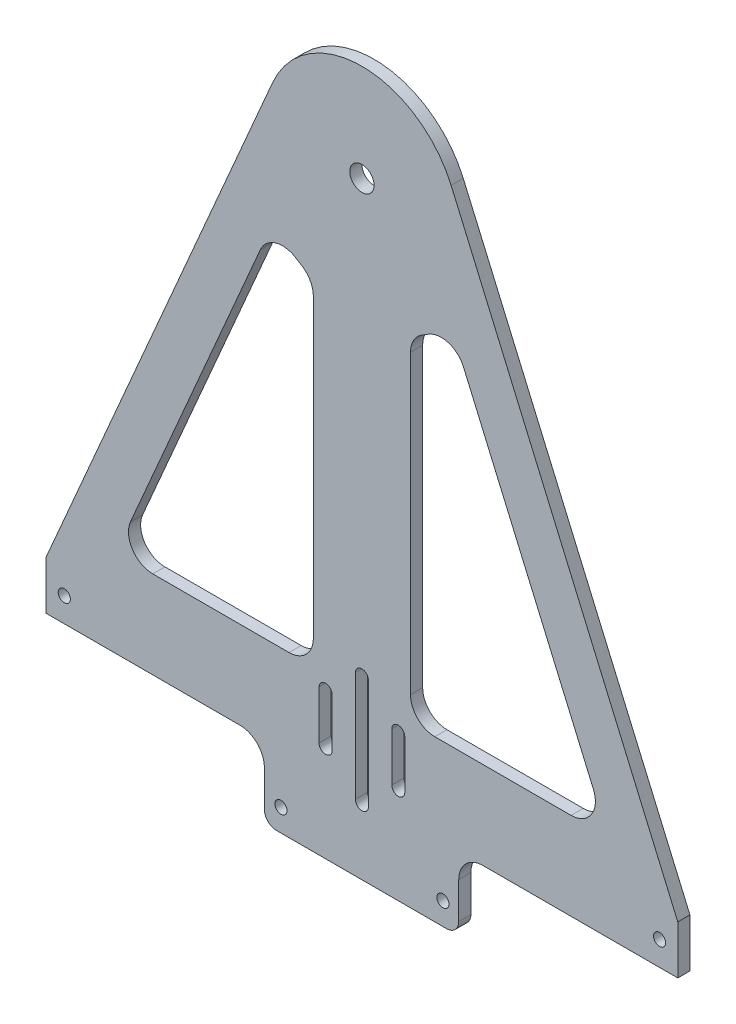
SolidWorks part; units mm, degrees
material "Hexcel AS4C (3000 Filaments)"
ref_plane "Front Plane" through (0, 0, 0) normal (0, 0, 1) x (1, 0, 0)
ref_plane "Top Plane" through (0, 0, 0) normal (0, 1, 0) x (1, 0, 0)
ref_plane "Right Plane" through (0, 0, 0) normal (1, 0, 0) x (0, 0, -1)
sketch "Sketch1" plane through (0, 0, 0) normal (0, 0, 1) x (1, 0, 0)
  line L0 (0, -58.42) -> (0, 58.42) construction
  line L2 (-82.55, 55.7897) -> (-82.55, -52.07)
  line L3 (-76.2, -58.42) -> (76.2, -58.42)
  line L4 (82.55, 55.7897) -> (82.55, -52.07)
  line L5 (-82.55, 58.42) -> (82.55, -58.42) construction
  line L6 (-82.55, -58.42) -> (82.55, 58.42) construction
  line L7 (-80.6901, 60.2799) -> (-75.4296, 65.5404)
  line L8 (-70.9395, 67.4003) -> (-50.8, 67.4003)
  line L9 (-46.3099, 65.5404) -> (-41.0494, 60.2799)
  line L10 (46.3099, 65.5404) -> (41.0494, 60.2799)
  line L11 (70.9395, 67.4003) -> (50.8, 67.4003)
  line L12 (80.6901, 60.2799) -> (75.4296, 65.5404)
  line L13 (-73.5697, 67.4003) -> (-82.55, 67.4003) construction
  line L14 (-82.55, 67.4003) -> (-82.55, 58.42) construction
  line L15 (-36.5592, 58.42) -> (0, 58.42)
  line L16 (0, 58.42) -> (36.5592, 58.42)
  circle A0 centre (-77.7875, -35.052) radius 1.5875
  circle A1 centre (-77.7875, -11.684) radius 1.5875
  circle A2 centre (-77.7875, 11.684) radius 1.5875
  circle A3 centre (-77.7875, 35.052) radius 1.5875
  circle A4 centre (77.7875, 35.052) radius 1.5875
  circle A5 centre (77.7875, 11.684) radius 1.5875
  circle A6 centre (77.7875, -11.684) radius 1.5875
  circle A7 centre (77.7875, -35.052) radius 1.5875
  arc A8 (82.55, 55.7897) -> (80.6901, 60.2799) centre (76.2, 55.7897) ccw
  arc A9 (75.4296, 65.5404) -> (70.9395, 67.4003) centre (70.9395, 61.0503) ccw
  arc A10 (46.3099, 65.5404) -> (50.8, 67.4003) centre (50.8, 61.0503) cw
  arc A11 (41.0494, 60.2799) -> (36.5592, 58.42) centre (36.5592, 64.77) cw
  arc A12 (-36.5592, 58.42) -> (-41.0494, 60.2799) centre (-36.5592, 64.77) cw
  arc A13 (-46.3099, 65.5404) -> (-50.8, 67.4003) centre (-50.8, 61.0503) ccw
  arc A14 (-70.9395, 67.4003) -> (-75.4296, 65.5404) centre (-70.9395, 61.0503) ccw
  arc A15 (-82.55, 55.7897) -> (-80.6901, 60.2799) centre (-76.2, 55.7897) cw
  arc A16 (76.2, -58.42) -> (82.55, -52.07) centre (76.2, -52.07) ccw
  arc A17 (-76.2, -58.42) -> (-82.55, -52.07) centre (-76.2, -52.07) cw
  circle A18 centre (-70.9395, 61.0503) radius 1.5875
  circle A19 centre (-50.8, 61.0503) radius 1.5875
  circle A20 centre (50.8, 61.0503) radius 1.5875
  circle A21 centre (70.9395, 61.0503) radius 1.5875
  point P0 (0, 0)
  point P36 (73.5697, 67.4003)
  point P39 (48.1697, 67.4003)
  point P42 (39.1895, 58.42)
  point P45 (-39.1895, 58.42)
  point P48 (-48.1697, 67.4003)
  dimension "D3" = 3.175
  dimension "D11" = 6.35
  dimension "D12" = 6.35
  dimension "D13" = 3.175
  dimension "D14" = 3.175
  dimension "D1" = 165.1
  dimension "D2" = 116.84
  dimension "D4" = 23.368
  dimension "D5" = 4.7625
  dimension "D7" = 46.736
  dimension "D8" = 12.7
  dimension "D9" = 135
  dimension "D10" = 25.4
  dimension "D6" = 4
extrude "Boss-Extrude1" [suppressed] add sketch "Sketch1" along normal blind 1.5
sketch "Sketch2" [suppressed] plane through (0, 0, 1.5) normal (0, 0, 1) x (1, 0, 0)
  line L0 (0, -45.72) -> (0, 6.3634) construction
  line L1 (0, -58.42) -> (0, 63.5) construction
  line L3 (-82.55, 1.8599) -> (82.55, 1.8599) construction
  line L4 (-82.55, 55.7897) -> (-82.55, -52.07) construction
  line L5 (82.55, -52.07) -> (82.55, 55.7897) construction
  line L7 (-76.2, -58.42) -> (76.2, -58.42) construction
  circle A0 centre (0, -45.72) radius 1.9062
  circle A1 centre (0, 6.3634) radius 1.9062
  dimension "D2" = 3.8125
  dimension "D3" = 3.8125
  dimension "D1" = 52.0834
  dimension "D4" = 12.7
extrude "Cut-Extrude1" [suppressed] cut sketch "Sketch2" against normal through all
sketch "Sketch3" [suppressed] plane through (0, 0, 1.5) normal (0, 0, 1) x (1, 0, 0)
  line L0 (0, 50.8) -> (0, 30.8) construction
  line L1 (-10, 40.8) -> (10, 40.8) construction
  line L2 (-10, 40.8) -> (0, 50.8) construction
  line L3 (0, 50.8) -> (10, 40.8) construction
  line L4 (10, 40.8) -> (0, 30.8) construction
  line L5 (0, 30.8) -> (-10, 40.8) construction
  line L6 (0, 63.5) -> (0, -58.42) construction
  line L8 (-76.2, -58.42) -> (76.2, -58.42) construction
  circle A0 centre (0, 50.8) radius 1.8669
  circle A1 centre (-10, 40.8) radius 1.8669
  circle A2 centre (0, 30.8) radius 1.8669
  circle A3 centre (10, 40.8) radius 1.8669
  dimension "D1" = 3.7338
  dimension "D2" = 12.7
extrude "Cut-Extrude2" [suppressed] cut sketch "Sketch3" against normal through all
sketch "Sketch4" [suppressed] plane through (0, 0, 1.5) normal (0, 0, 1) x (1, 0, 0)
  line L0 (0, 58.42) -> (0, -58.42) construction
  line L1 (36.5592, 58.42) -> (-36.5592, 58.42) construction
  line L2 (-76.2, -58.42) -> (76.2, -58.42) construction
  line L5 (0, 33.045) -> (0, 52.045) construction
  line L6 (-9.5, 42.545) -> (9.5, 42.545) construction
  circle A14 centre (0, 42.545) radius 8 construction
  circle A15 centre (0, 42.545) radius 9.5 construction
  circle A16 centre (0, 50.545) radius 1.5
  circle A17 centre (0, 34.545) radius 1.5
  circle A18 centre (-9.5, 42.545) radius 1.5
  circle A19 centre (9.5, 42.545) radius 1.5
  dimension "D1" = 15.875
  dimension "D3" = 16
  dimension "D4" = 19
  dimension "D5" = 3
  dimension "D6" = 3
  dimension "D7" = 3
  dimension "D8" = 3
extrude "Cut-Extrude3" [suppressed] cut sketch "Sketch4" against normal through all
sketch "Sketch5" plane through (0, 0, 0) normal (0, 0, 1) x (1, 0, 0)
  line L0 (0, 70.8856) -> (0, 39.1356) construction
  line L1 (-82.55, 70.8856) -> (82.55, 70.8856) construction
  line L2 (-82.55, 70.8856) -> (-82.55, 58.1856)
  line L4 (82.55, 70.8856) -> (82.55, 58.1856)
  line L5 (82.55, 70.8856) -> (23.3162, 207.9611)
  line L8 (77.7875, 58.1856) -> (77.7875, 70.8856) construction
  line L11 (0, -48.26) -> (0, -46.3538) construction
  line L12 (0, 70.8856) -> (0, 197.8856) construction
  line L14 (-82.55, 58.1856) -> (-31.849, 58.1856)
  line L15 (-22.324, 39.1356) -> (22.126, 39.1356)
  line L16 (-25.499, 42.3106) -> (-25.499, 51.8356)
  line L17 (25.301, 42.3106) -> (25.301, 51.8356)
  line L18 (31.651, 58.1856) -> (82.55, 58.1856)
  line L19 (-82.55, 70.8856) -> (-23.3162, 207.9611)
  line L20 (-77.7875, 58.1856) -> (-77.7875, 70.8856) construction
  line L23 (0, -0.6801) -> (0, 0) construction
  line L24 (0, 39.1356) -> (0, 70.8856) construction
  line L26 (0, 70.8856) -> (-82.55, 70.8856) construction
  line L27 (-60.4921, 89.9145) -> (-26.56, 168.4383)
  line L28 (0, -48.26) -> (0, -46.3538) construction
  line L37 (68.715, 70.8856) -> (11.6581, 202.9234) construction
  line L38 (31.651, 70.8856) -> (68.715, 70.8856) construction
  line L39 (12.601, 51.8356) -> (12.601, 51.8356) construction
  line L40 (-12.799, 51.8356) -> (12.601, 51.8356) construction
  line L41 (-12.799, 51.8356) -> (-12.799, 51.8356) construction
  line L42 (-68.715, 70.8856) -> (-31.849, 70.8856) construction
  line L43 (-12.7, 87.3956) -> (-12.7, 164.89)
  line L44 (-68.715, 70.8856) -> (-11.6581, 202.9234) construction
  line L45 (68.715, 70.8856) -> (68.715, 70.8856) construction
  line L46 (-54.6631, 81.0456) -> (-19.05, 81.0456)
  line L47 (-12.7, 70.8856) -> (-12.7, 197.8856) construction
  line L48 (19.05, 81.0456) -> (54.6631, 81.0456) construction
  line L49 (-82.55, 81.0456) -> (82.55, 81.0456) construction
  line L50 (-68.715, 70.8856) -> (-68.715, 70.8856) construction
  line L51 (60.4921, 89.9145) -> (26.56, 168.4383)
  line L52 (54.6631, 81.0456) -> (19.05, 81.0456)
  line L53 (12.7, 87.3956) -> (12.7, 164.89)
  line L54 (-11.2, 64.4741) -> (-11.2, 77.1741)
  line L55 (-7.8, 64.4741) -> (-7.8, 77.1741)
  line L56 (-1.7, 56.4741) -> (-1.7, 85.1741)
  line L57 (1.7, 56.4741) -> (1.7, 85.1741)
  line L58 (7.8, 64.4741) -> (7.8, 77.1741)
  line L59 (11.2, 64.4741) -> (11.2, 77.1741)
  arc A12 (-25.499, 51.8356) -> (-31.849, 58.1856) centre (-31.849, 51.8356) ccw
  arc A13 (25.301, 51.8356) -> (31.651, 58.1856) centre (31.651, 51.8356) cw
  arc A14 (25.301, 42.3106) -> (22.126, 39.1356) centre (22.126, 42.3106) cw
  arc A15 (-25.499, 42.3106) -> (-22.324, 39.1356) centre (-22.324, 42.3106) ccw
  circle A16 centre (-77.7875, 64.5356) radius 1.5875
  circle A17 centre (77.7875, 64.5356) radius 1.5875
  arc A18 (23.3162, 207.9611) -> (-23.3162, 207.9611) centre (0, 197.8856) ccw
  circle A19 centre (0, 197.8856) radius 25.4 construction
  arc A25 (11.6581, 202.9234) -> (-11.6581, 202.9234) centre (0, 197.8856) ccw construction
  arc A26 (12.601, 51.8356) -> (31.651, 70.8856) centre (31.651, 51.8356) cw construction
  arc A27 (-12.799, 51.8356) -> (-31.849, 70.8856) centre (-31.849, 51.8356) ccw construction
  arc A28 (12.601, 51.8356) -> (12.601, 51.8356) centre (12.601, 51.8356) cw construction
  arc A29 (-12.799, 51.8356) -> (-12.799, 51.8356) centre (-12.799, 51.8356) ccw construction
  arc A30 (-17.2758, 171.2471) -> (-15.875, 170.3893) centre (0, 197.8856) ccw
  arc A31 (-17.2758, 171.2471) -> (-26.56, 168.4383) centre (-20.7309, 165.9194) ccw
  circle A32 centre (0, 197.8856) radius 31.75 construction
  arc A33 (-15.875, 170.3893) -> (-12.7, 164.89) centre (-19.05, 164.89) cw
  arc A34 (-19.05, 81.0456) -> (-12.7, 87.3956) centre (-19.05, 87.3956) ccw
  arc A35 (-54.6631, 81.0456) -> (-60.4921, 89.9145) centre (-54.6631, 87.3956) cw
  arc A36 (15.875, 170.3893) -> (12.7, 164.89) centre (19.05, 164.89) ccw
  arc A37 (17.2758, 171.2471) -> (15.875, 170.3893) centre (0, 197.8856) cw
  arc A38 (17.2758, 171.2471) -> (26.56, 168.4383) centre (20.7309, 165.9194) cw
  arc A39 (54.6631, 81.0456) -> (60.4921, 89.9145) centre (54.6631, 87.3956) ccw
  arc A40 (19.05, 81.0456) -> (12.7, 87.3956) centre (19.05, 87.3956) cw
  circle A57 centre (0, 64.4741) radius 8 construction
  circle A58 centre (0, 64.4741) radius 9.5 construction
  arc A59 (7.8, 64.4741) -> (11.2, 64.4741) centre (9.5, 64.4741) ccw
  arc A60 (-11.2, 64.4741) -> (-7.8, 64.4741) centre (-9.5, 64.4741) ccw
  arc A62 (-1.7, 56.4741) -> (1.7, 56.4741) centre (0, 56.4741) ccw
  arc A63 (-7.8, 77.1741) -> (-11.2, 77.1741) centre (-9.5, 77.1741) ccw
  arc A64 (11.2, 77.1741) -> (7.8, 77.1741) centre (9.5, 77.1741) ccw
  arc A65 (1.7, 85.1741) -> (-1.7, 85.1741) centre (0, 85.1741) ccw
  circle A66 centre (-21.1667, 44.969) radius 1.5875
  circle A67 centre (21.1667, 44.969) radius 1.5875
  circle A68 centre (0, 197.8856) radius 3.175
  point P0 (0, 0)
  point P52 (25.301, 58.1856)
  point P55 (25.301, 39.1356)
  point P58 (-25.499, 39.1356)
  point P68 (30.3627, 182.0028)
  dimension "D17" = 6.35
  dimension "D18" = 6.35
  dimension "D19" = 3.175
  dimension "D20" = 3.175
  dimension "D21" = 3.175
  dimension "D4" = 50.8
  dimension "D24" = 6.35
  dimension "D25" = 16
  dimension "D26" = 19
  dimension "D27" = 3.4
  dimension "D28" = 3.4
  dimension "D30" = 3.4
  dimension "D31" = 3.4
  dimension "D32" = 3.4
  dimension "D35" = 3.4
  dimension "D36" = 3.175
  dimension "D9" = 6.35
  dimension "D14" = 12.7
  dimension "D15" = 50.8
  dimension "D16" = 19.05
  dimension "D22" = 6.35
  dimension "D3" = 127
  dimension "D33" = 12.7
  dimension "D34" = 12.7
  dimension "D8" = 25.9166
  dimension "D10" = 165.1
  dimension "D6" = 6.35
  dimension "D7" = 12.7
  dimension "D23" = 10.16
extrude "Boss-Extrude2" add sketch "Sketch5" along normal blind 3.175
equation "\"Top Plate Width\" = 4.5in"
equation "\"Plate Width\" = 3.5in"
equation "\"Plate Thickness\" = 0.375in"
equation "\"Num holes\" = 4"
equation "\"Plate Height\" = 1.25in"
equation "\"Plate Clearance Hole Diameter\" = 0.125in"
equation "\"D3@Sketch1\"=\"Plate Clearance Hole Diameter\""
equation "\"Hole Spacing\"= \"Plate Width\" / ( \"Num holes\" + 1 )"
equation "\"Plate Tap Hole Diameter\" = 0.116in"
equation "\"Bottom Plate Length\" = 6.5in"
equation "\"D21@Sketch5\"=\"Plate Clearance Hole Diameter\""
equation "\"Number Eight Clearance Size\" = 0.177in"
equation "\"Back Brace Height\" = 1.1962912in"
equation "\"Titanium Offset Length\" = 5in"
equation "\"Titanium Head Radius\" = 2in"
equation "\"D3@Sketch5\"=\"Titanium Offset Length\""
equation "\"D4@Sketch5\"=\"Titanium Head Radius\""
equation "\"Titanium Plate Border Thickness\" = 0.5in"
equation "\"D5@Sketch5\"=\"Titanium Plate Border Thickness\""
equation "\"D6@Sketch5\"=\"Titanium Plate Border Thickness\" / 2"
equation "\"D23@Sketch5\"=\"Titanium Plate Border Thickness\"/1.25"
equation "\"slot_hole_length\"=0.75"
